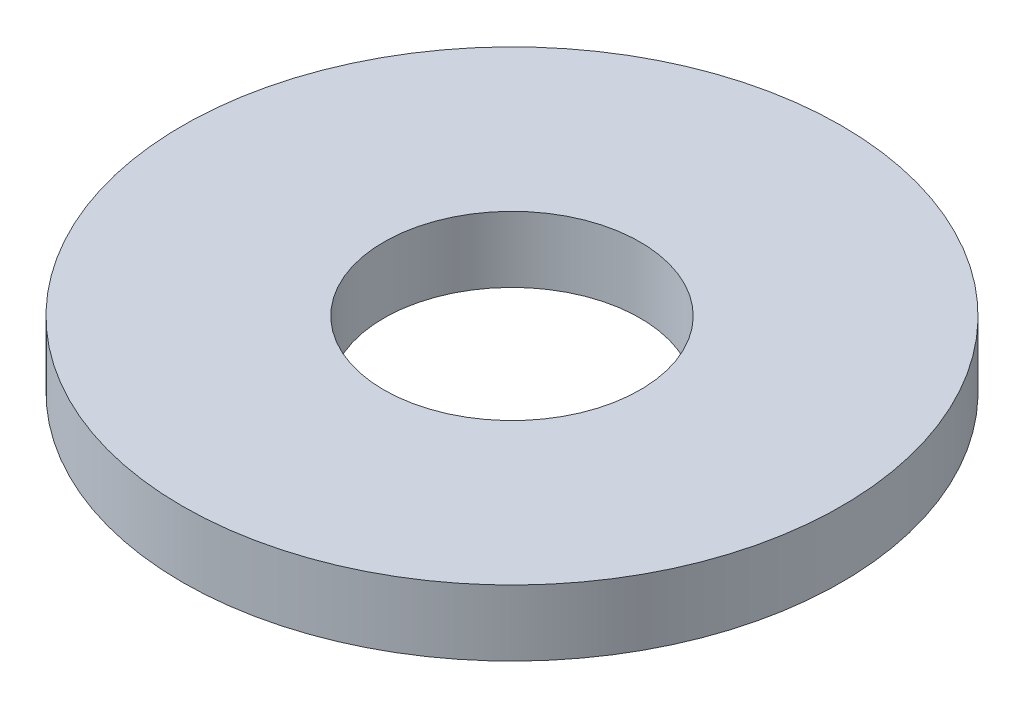
SolidWorks part; units mm, degrees
ref_plane "Front Plane" through (0, 0, 0) normal (0, 0, 1) x (1, 0, 0)
ref_plane "Top Plane" through (0, 0, 0) normal (0, 1, 0) x (1, 0, 0)
ref_plane "Right Plane" through (0, 0, 0) normal (1, 0, 0) x (0, 0, -1)
sketch "Sketch1" plane through (0, 0, 0) normal (0, 1, 0) x (1, 0, 0)
  circle A0 centre (0, 0) radius 45
  dimension "FLANGE_OD" = 90
extrude "Boss-Extrude1" add sketch "Sketch1" along normal blind 9
sketch "Sketch2" plane through (0, 0, 0) normal (0, 1, 0) x (1, 0, 0)
  circle A0 centre (0, 0) radius 17.5
  dimension "BORE_D" = 35
extrude "Cut-Extrude1" cut sketch "Sketch2" along normal through all
sketch "Sketch3" plane through (0, 9, 0) normal (0, 1, 0) x (1, 0, 0)
  circle A0 centre (0, 0) radius 13.0377 construction
  circle A1 centre (-13.0377, 0) radius 3.06
  dimension "BOLT_D" = 6.12
  dimension "BOLT_PCD" = 26.0754
extrude "Cut-Extrude2" cut sketch "Sketch3" against normal blind 8.1464 rebuild error yes
pattern_circular "CirPattern1" count 5 over 360 rebuild error yes
